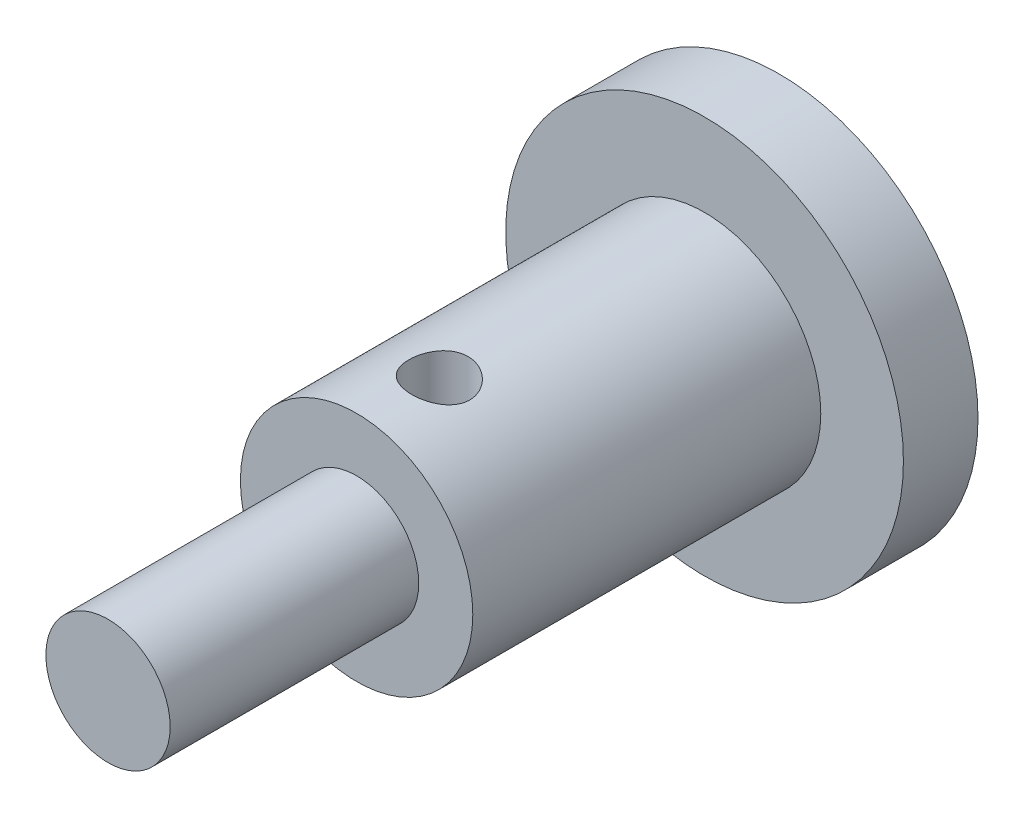
SolidWorks part; units mm, degrees
ref_plane "Front Plane" through (0, 0, 0) normal (0, 0, 1) x (1, 0, 0)
ref_plane "Top Plane" through (0, 0, 0) normal (0, 1, 0) x (1, 0, 0)
ref_plane "Right Plane" through (0, 0, 0) normal (1, 0, 0) x (0, 0, -1)
sketch "Sketch1" plane through (0, 0, 0) normal (0, 0, 1) x (1, 0, 0)
  circle A0 centre (0, 0) radius 8
  dimension "D1" = 16
extrude "Boss-Extrude1" add sketch "Sketch1" along normal blind 3
sketch "Sketch2" plane through (0, 0, 3) normal (0, 0, 1) x (1, 0, 0)
  circle A0 centre (0, 0) radius 4.675
  dimension "D1" = 9.35
extrude "Boss-Extrude2" add sketch "Sketch2" along normal blind 14
sketch "Sketch3" plane through (0, 0, 17) normal (0, 0, 1) x (1, 0, 0)
  circle A0 centre (0, 0) radius 2.5
  dimension "D1" = 5
extrude "Boss-Extrude3" add sketch "Sketch3" along normal blind 10
sketch "Sketch4" plane through (0, 0, 0) normal (0, 1, 0) x (1, 0, 0)
  line L0 (-4.675, -3) -> (-4.675, -17) construction
  circle A0 centre (0.325, -13.9962) radius 1.225
  dimension "D2" = 2.45
  dimension "D1" = 5
  dimension "D3" = 14
extrude "Cut-Extrude1" cut sketch "Sketch4" against normal mid plane 15
